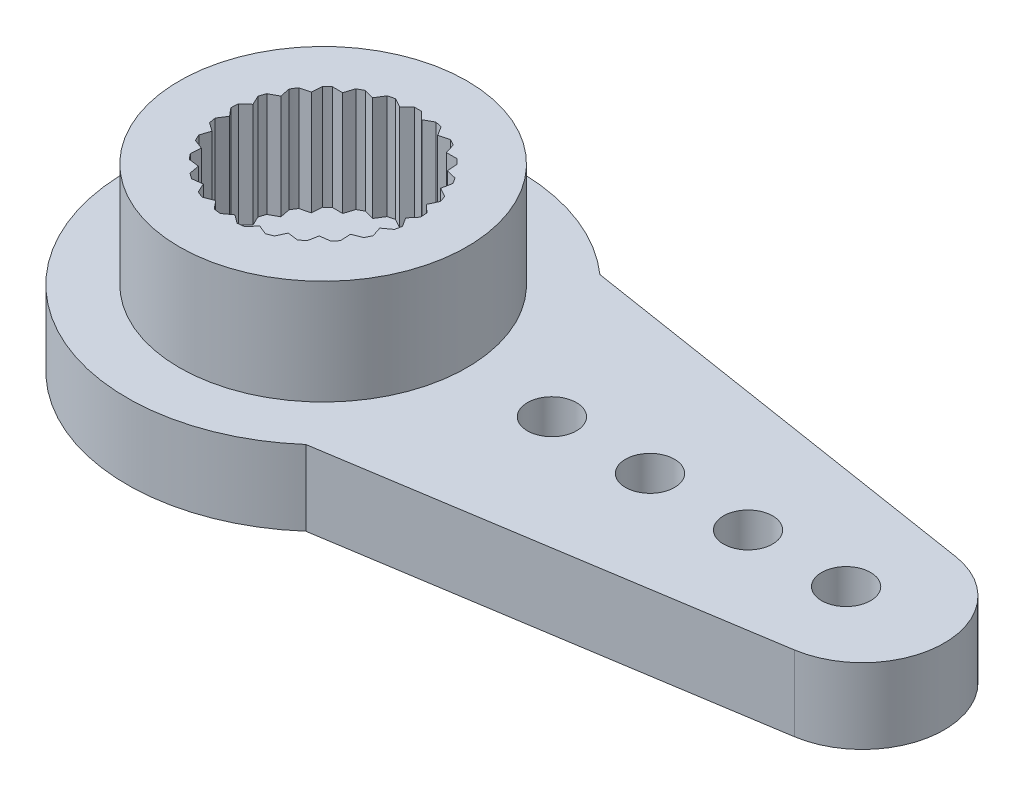
SolidWorks part; units mm, degrees
note: '?' marks a value the reader was unsure of.
material "ABS"
ref_plane "Front Plane" through (0, 0, 0) normal (0, 0, 1) x (1, 0, 0)
ref_plane "Top Plane" through (0, 0, 0) normal (0, 1, 0) x (1, 0, 0)
ref_plane "Right Plane" through (0, 0, 0) normal (1, 0, 0) x (0, 0, -1)
sketch "Sketch2" plane through (0, 0, 0) normal (0, 1, 0) x (1, 0, 0)
  circle A0 centre (0, 0) radius 6
  circle A1 centre (0, 0) radius 1.5
  dimension "D1" = 12
  dimension "D2" = 3
extrude "Boss-Extrude1" add sketch "Sketch2" along normal mid plane 2.3
sketch "Sketch3" plane through (0, 1.15, 0) normal (0, 1, 0) x (1, 0, 0)
  line L0 (0, 0) -> (0, 2.9) construction
  line L3 (0, 0) -> (0.376, 2.9763) construction
  line L52 (0.1074, 2.898) -> (0.3384, 2.6787)
  line L53 (-0.1074, 2.898) -> (-0.3384, 2.6787)
  line L54 (0.8248, 2.7802) -> (0.9939, 2.5104)
  line L55 (0.6167, 2.8337) -> (0.3384, 2.6787)
  line L56 (1.4903, 2.4878) -> (1.587, 2.1843)
  line L57 (1.302, 2.5913) -> (0.9939, 2.5104)
  line L58 (2.0621, 2.039) -> (2.0804, 1.721)
  line L59 (1.9055, 2.1861) -> (1.587, 2.1843)
  line L60 (2.5044, 1.4621) -> (2.443, 1.1496)
  line L61 (2.3893, 1.6435) -> (2.0804, 1.721)
  line L62 (2.7894, 0.7934) -> (2.6522, 0.5059)
  line L63 (2.723, 0.9977) -> (2.443, 1.1496)
  line L64 (2.899, 0.0748) -> (2.6947, -0.1695)
  line L65 (2.8855, 0.2892) -> (2.6522, 0.5059)
  line L66 (2.8265, -0.6486) -> (2.5679, -0.8343)
  line L67 (2.8668, -0.4375) -> (2.6947, -0.1695)
  line L68 (2.5765, -1.3311) -> (2.2797, -1.4467)
  line L69 (2.6679, -1.1367) -> (2.5679, -0.8343)
  line L70 (2.1645, -1.93) -> (1.8483, -1.9682)
  line L71 (2.3014, -1.7645) -> (2.2797, -1.4467)
  line L72 (1.6165, -2.4077) -> (1.3007, -2.366)
  line L73 (1.7903, -2.2814) -> (1.8483, -1.9682)
  line L74 (0.967, -2.734) -> (0.6715, -2.6152)
  line L75 (1.1667, -2.655) -> (1.3007, -2.366)
  line L76 (0.2566, -2.8886) -> (0, -2.7)
  line L77 (0.4698, -2.8617) -> (0.6715, -2.6152)
  line L78 (-0.4698, -2.8617) -> (-0.6715, -2.6152)
  line L79 (-0.2566, -2.8886) -> (0, -2.7)
  line L80 (-1.1667, -2.655) -> (-1.3007, -2.366)
  line L81 (-0.967, -2.734) -> (-0.6715, -2.6152)
  line L82 (-1.7903, -2.2814) -> (-1.8483, -1.9682)
  line L83 (-1.6165, -2.4077) -> (-1.3007, -2.366)
  line L84 (-2.3014, -1.7645) -> (-2.2797, -1.4467)
  line L85 (-2.1645, -1.93) -> (-1.8483, -1.9682)
  line L86 (-2.6679, -1.1367) -> (-2.5679, -0.8343)
  line L87 (-2.5765, -1.3311) -> (-2.2797, -1.4467)
  line L88 (-2.8668, -0.4375) -> (-2.6947, -0.1695)
  line L89 (-2.8265, -0.6486) -> (-2.5679, -0.8343)
  line L90 (-2.8855, 0.2892) -> (-2.6522, 0.5059)
  line L91 (-2.899, 0.0748) -> (-2.6947, -0.1695)
  line L92 (-2.723, 0.9977) -> (-2.443, 1.1496)
  line L93 (-2.7894, 0.7934) -> (-2.6522, 0.5059)
  line L94 (-2.3893, 1.6435) -> (-2.0804, 1.721)
  line L95 (-2.5044, 1.4621) -> (-2.443, 1.1496)
  line L96 (-1.9055, 2.1861) -> (-1.587, 2.1843)
  line L97 (-2.0621, 2.039) -> (-2.0804, 1.721)
  line L98 (-1.302, 2.5913) -> (-0.9939, 2.5104)
  line L99 (-1.4903, 2.4878) -> (-1.587, 2.1843)
  line L100 (-0.6167, 2.8337) -> (-0.3384, 2.6787)
  line L101 (-0.8248, 2.7802) -> (-0.9939, 2.5104)
  line L102 (-2.533, 1.6075) -> (-2.3893, 1.6435) construction
  line L103 (-2.533, 1.6075) -> (-2.5044, 1.4621) construction
  line L104 (-2.8532, 0.9271) -> (-2.723, 0.9977) construction
  line L105 (-2.8532, 0.9271) -> (-2.7894, 0.7934) construction
  line L106 (-2.9941, 0.1884) -> (-2.8855, 0.2892) construction
  line L107 (-2.9941, 0.1884) -> (-2.899, 0.0748) construction
  line L108 (-2.9469, -0.5621) -> (-2.8668, -0.4375) construction
  line L109 (-2.9469, -0.5621) -> (-2.8265, -0.6486) construction
  line L110 (0, 3) -> (0.1074, 2.898) construction
  line L111 (0, 2.9) -> (0, 3) construction
  line L112 (0, 3) -> (-0.1074, 2.898) construction
  line L113 (-0.7461, 2.9057) -> (-0.6167, 2.8337) construction
  line L114 (-0.7461, 2.9057) -> (-0.8248, 2.7802) construction
  line L115 (-1.4453, 2.6289) -> (-1.302, 2.5913) construction
  line L116 (-1.4453, 2.6289) -> (-1.4903, 2.4878) construction
  line L117 (-2.0536, 2.1869) -> (-1.9055, 2.1861) construction
  line L118 (-2.0536, 2.1869) -> (-2.0621, 2.039) construction
  line L119 (-2.7145, -1.2773) -> (-2.6679, -1.1367) construction
  line L120 (-2.7145, -1.2773) -> (-2.5765, -1.3311) construction
  line L121 (-2.3115, -1.9123) -> (-2.3014, -1.7645) construction
  line L122 (-2.3115, -1.9123) -> (-2.1645, -1.93) construction
  line L123 (-1.7634, -2.4271) -> (-1.7903, -2.2814) construction
  line L124 (-1.7634, -2.4271) -> (-1.6165, -2.4077) construction
  line L125 (-1.1044, -2.7893) -> (-1.1667, -2.655) construction
  line L126 (-1.1044, -2.7893) -> (-0.967, -2.734) construction
  line L127 (-0.376, -2.9763) -> (-0.4698, -2.8617) construction
  line L128 (-0.376, -2.9763) -> (-0.2566, -2.8886) construction
  line L129 (0.376, -2.9763) -> (0.2566, -2.8886) construction
  line L130 (0.376, -2.9763) -> (0.4698, -2.8617) construction
  line L131 (1.1044, -2.7893) -> (0.967, -2.734) construction
  line L132 (1.1044, -2.7893) -> (1.1667, -2.655) construction
  line L133 (1.7634, -2.4271) -> (1.6165, -2.4077) construction
  line L134 (1.7634, -2.4271) -> (1.7903, -2.2814) construction
  line L135 (2.3115, -1.9123) -> (2.3014, -1.7645) construction
  line L136 (2.3115, -1.9123) -> (2.1645, -1.93) construction
  line L137 (2.7145, -1.2773) -> (2.6679, -1.1367) construction
  line L138 (2.7145, -1.2773) -> (2.5765, -1.3311) construction
  line L139 (2.9469, -0.5621) -> (2.8668, -0.4375) construction
  line L140 (2.9469, -0.5621) -> (2.8265, -0.6486) construction
  line L141 (2.9941, 0.1884) -> (2.8855, 0.2892) construction
  line L142 (2.9941, 0.1884) -> (2.899, 0.0748) construction
  line L143 (2.8532, 0.9271) -> (2.723, 0.9977) construction
  line L144 (2.8532, 0.9271) -> (2.7894, 0.7934) construction
  line L145 (2.533, 1.6075) -> (2.3893, 1.6435) construction
  line L146 (2.533, 1.6075) -> (2.5044, 1.4621) construction
  line L147 (2.0536, 2.1869) -> (1.9055, 2.1861) construction
  line L148 (2.0536, 2.1869) -> (2.0621, 2.039) construction
  line L149 (1.4453, 2.6289) -> (1.302, 2.5913) construction
  line L150 (1.4453, 2.6289) -> (1.4903, 2.4878) construction
  line L151 (0.7461, 2.9057) -> (0.6167, 2.8337) construction
  line L152 (0.7461, 2.9057) -> (0.8248, 2.7802) construction
  circle A0 centre (0, 0) radius 4.4
  circle A1 centre (0, 0) radius 3 construction
  circle A2 centre (0, 0) radius 2.7 construction
  arc A3 (-0.6167, 2.8337) -> (-0.8248, 2.7802) centre (0, 0) ccw
  arc A4 (-0.1074, 2.898) -> (-0.6167, 2.8337) centre (0, 0) ccw construction
  arc A5 (-0.8248, 2.7802) -> (-1.302, 2.5913) centre (0, 0) ccw construction
  arc A6 (-1.302, 2.5913) -> (-1.4903, 2.4878) centre (0, 0) ccw
  arc A7 (-1.4903, 2.4878) -> (-1.9055, 2.1861) centre (0, 0) ccw construction
  arc A8 (-1.9055, 2.1861) -> (-2.0621, 2.039) centre (0, 0) ccw
  arc A9 (-2.0621, 2.039) -> (-2.3893, 1.6435) centre (0, 0) ccw construction
  arc A10 (-2.3893, 1.6435) -> (-2.5044, 1.4621) centre (0, 0) ccw
  arc A11 (-2.5044, 1.4621) -> (-2.723, 0.9977) centre (0, 0) ccw construction
  arc A12 (-2.723, 0.9977) -> (-2.7894, 0.7934) centre (0, 0) ccw
  arc A13 (-2.7894, 0.7934) -> (-2.8855, 0.2892) centre (0, 0) ccw construction
  arc A14 (-2.8855, 0.2892) -> (-2.899, 0.0748) centre (0, 0) ccw
  arc A15 (-2.899, 0.0748) -> (-2.8668, -0.4375) centre (0, 0) ccw construction
  arc A16 (-2.8668, -0.4375) -> (-2.8265, -0.6486) centre (0, 0) ccw
  arc A17 (-2.8265, -0.6486) -> (-2.6679, -1.1367) centre (0, 0) ccw construction
  arc A18 (-2.6679, -1.1367) -> (-2.5765, -1.3311) centre (0, 0) ccw
  arc A19 (-2.5765, -1.3311) -> (-2.3014, -1.7645) centre (0, 0) ccw construction
  arc A20 (-2.3014, -1.7645) -> (-2.1645, -1.93) centre (0, 0) ccw
  arc A21 (-2.1645, -1.93) -> (-1.7903, -2.2814) centre (0, 0) ccw construction
  arc A22 (-1.7903, -2.2814) -> (-1.6165, -2.4077) centre (0, 0) ccw
  arc A23 (-1.6165, -2.4077) -> (-1.1667, -2.655) centre (0, 0) ccw construction
  arc A24 (-1.1667, -2.655) -> (-0.967, -2.734) centre (0, 0) ccw
  arc A25 (-0.967, -2.734) -> (-0.4698, -2.8617) centre (0, 0) ccw construction
  arc A26 (-0.4698, -2.8617) -> (-0.2566, -2.8886) centre (0, 0) ccw
  arc A27 (-0.2566, -2.8886) -> (0.2566, -2.8886) centre (0, 0) ccw construction
  arc A28 (0.2566, -2.8886) -> (0.4698, -2.8617) centre (0, 0) ccw
  arc A29 (0.4698, -2.8617) -> (0.967, -2.734) centre (0, 0) ccw construction
  arc A30 (0.967, -2.734) -> (1.1667, -2.655) centre (0, 0) ccw
  arc A31 (1.1667, -2.655) -> (1.6165, -2.4077) centre (0, 0) ccw construction
  arc A32 (1.6165, -2.4077) -> (1.7903, -2.2814) centre (0, 0) ccw
  arc A33 (1.7903, -2.2814) -> (2.1645, -1.93) centre (0, 0) ccw construction
  arc A34 (2.1645, -1.93) -> (2.3014, -1.7645) centre (0, 0) ccw
  arc A35 (2.3014, -1.7645) -> (2.5765, -1.3311) centre (0, 0) ccw construction
  arc A36 (2.5765, -1.3311) -> (2.6679, -1.1367) centre (0, 0) ccw
  arc A37 (2.6679, -1.1367) -> (2.8265, -0.6486) centre (0, 0) ccw construction
  arc A38 (2.8265, -0.6486) -> (2.8668, -0.4375) centre (0, 0) ccw
  arc A39 (2.8668, -0.4375) -> (2.899, 0.0748) centre (0, 0) ccw construction
  arc A40 (2.899, 0.0748) -> (2.8855, 0.2892) centre (0, 0) ccw
  arc A41 (2.8855, 0.2892) -> (2.7894, 0.7934) centre (0, 0) ccw construction
  arc A42 (2.7894, 0.7934) -> (2.723, 0.9977) centre (0, 0) ccw
  arc A43 (2.723, 0.9977) -> (2.5044, 1.4621) centre (0, 0) ccw construction
  arc A44 (2.5044, 1.4621) -> (2.3893, 1.6435) centre (0, 0) ccw
  arc A45 (2.3893, 1.6435) -> (2.0621, 2.039) centre (0, 0) ccw construction
  arc A46 (2.0621, 2.039) -> (1.9055, 2.1861) centre (0, 0) ccw
  arc A47 (1.9055, 2.1861) -> (1.4903, 2.4878) centre (0, 0) ccw construction
  arc A48 (1.4903, 2.4878) -> (1.302, 2.5913) centre (0, 0) ccw
  arc A49 (1.302, 2.5913) -> (0.8248, 2.7802) centre (0, 0) ccw construction
  arc A50 (0.8248, 2.7802) -> (0.6167, 2.8337) centre (0, 0) ccw
  arc A51 (0.3635, 2.8771) -> (0.1074, 2.898) centre (0, 0) ccw construction
  arc A52 (0.1074, 2.898) -> (-0.1074, 2.898) centre (0, 0) ccw
  arc A53 (0.6167, 2.8337) -> (0.3635, 2.8771) centre (0, 0) ccw construction
  point P84 (0, 0)
  dimension "D1" = 8.8
  dimension "D2" = 5.4
  dimension "D3" = 6
  dimension "D6" = 5.8
  dimension "D4" = 7.2
  dimension "D5" = 25
extrude "Boss-Extrude2" add sketch "Sketch3" along normal blind 3.2
sketch "Sketch4" plane through (0, 0, 0) normal (0, 1, 0) x (1, 0, 0)
  line L0 (0, 0) -> (16, 0) construction
  line L1 (3.9686, 4.5) -> (16.8881, 2.4697)
  line L2 (3.9686, -4.5) -> (16.8881, -2.4697)
  line L3 (16, 0) -> (13, 0) construction
  circle A0 centre (0, 0) radius 6 construction
  arc A1 (3.9686, -4.5) -> (3.9686, 4.5) centre (0, 0) ccw
  arc A2 (16.8881, 2.4697) -> (16.8881, -2.4697) centre (16.5, 0) cw
  circle A3 centre (16, 0) radius 0.75
  circle A4 centre (13, 0) radius 0.75
  circle A5 centre (10, 0) radius 0.75
  circle A6 centre (7, 0) radius 0.75
  dimension "D3" = 2.5
  dimension "D5" = 1.5
  dimension "D2" = 9
  dimension "D7" = 3
  dimension "D4" = 0.5
  dimension "D1" = 16
  dimension "D6" = 4
extrude "Boss-Extrude3" add sketch "Sketch4" along normal mid plane 2.3
pattern_circular "CirPattern1" [suppressed] count 1 over? 360?
sketch "Sketch5" [suppressed] plane through (0, 0, 0) normal (0, 1, 0) x (1, 0, 0)
  line L0 (3, 7) -> (-3, 7) construction
  circle A0 centre (0, 0) radius 10
  circle A1 centre (0, 7) radius 0.75
  circle A2 centre (-3, 7) radius 0.75
  circle A3 centre (3, 7) radius 0.75
  circle A4 centre (7, 3) radius 0.75
  circle A5 centre (7, 0) radius 0.75
  circle A6 centre (7, -3) radius 0.75
  circle A7 centre (3, -7) radius 0.75
  circle A8 centre (0, -7) radius 0.75
  circle A9 centre (-3, -7) radius 0.75
  circle A10 centre (-7, -3) radius 0.75
  circle A11 centre (-7, 0) radius 0.75
  circle A12 centre (-7, 3) radius 0.75
  circle A13 centre (0, 0) radius 1.5 construction
  circle A14 centre (0, 0) radius 1.5
  point P8 (0, 7)
  point P31 (0, 0)
  dimension "D1" = 1.5
  dimension "D3" = 2.25
  dimension "D4" = 6
  dimension "D2" = 7
  dimension "D5" = 4
extrude "Boss-Extrude4" [suppressed] add sketch "Sketch5" along normal mid plane 2.3
equation "\"N_hole\"= 4"
equation "\"N_horn\"= 1"
equation "\"D6@Sketch4\"=\"N_hole\""
equation "\"D1@CirPattern1\"=\"N_horn\""
equation "\"D1@Sketch4\"=(\"N_hole\" - 1) *3 +7"
